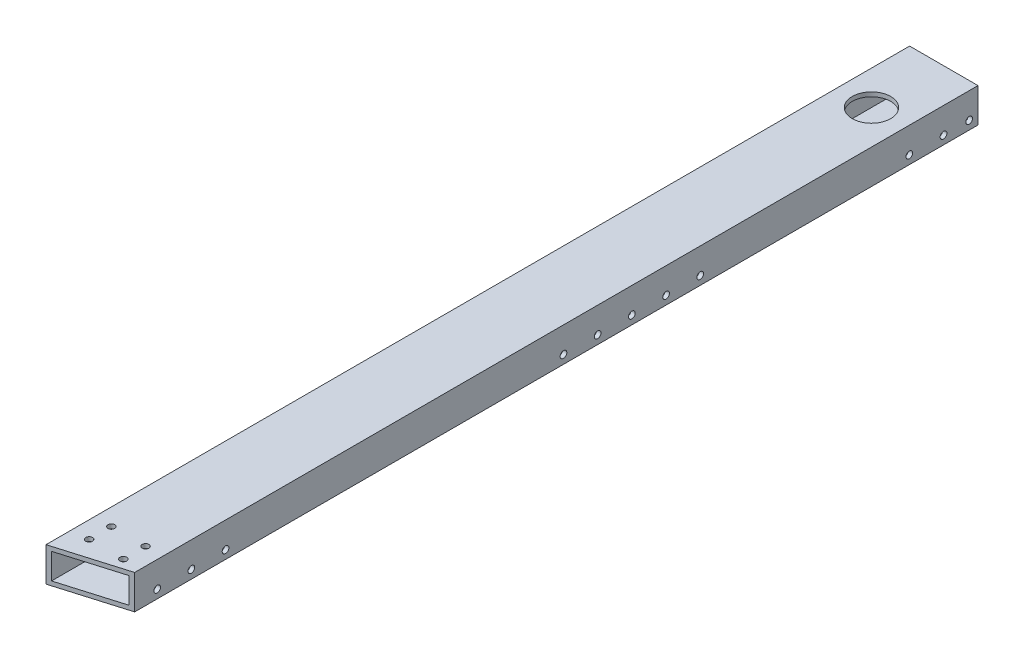
SolidWorks part; units mm, degrees
ref_plane "Front Plane" through (0, 0, 0) normal (0, 0, 1) x (1, 0, 0)
ref_plane "Top Plane" through (0, 0, 0) normal (0, 1, 0) x (1, 0, 0)
ref_plane "Right Plane" through (0, 0, 0) normal (1, 0, 0) x (0, 0, -1)
sketch "Sketch1" plane through (0, 0, 0) normal (0, 0, 1) x (1, 0, 0)
  line L0 (-22.225, 9.525) -> (22.225, 9.525)
  line L2 (-25.4, 12.7) -> (25.4, 12.7)
  line L3 (-25.4, 12.7) -> (-25.4, -12.7)
  line L4 (-25.4, -12.7) -> (25.4, -12.7)
  line L5 (25.4, 12.7) -> (25.4, -12.7)
  line L10 (22.225, 9.525) -> (22.225, -9.525)
  line L11 (-22.225, -9.525) -> (22.225, -9.525)
  line L12 (-22.225, 9.525) -> (-22.225, -9.525)
  point P12 (0, 12.7)
  point P14 (25.4, 0)
  dimension "Wall Thickness" = 3.175
  dimension "Outside Width" = 50.8
  dimension "Outside Height" = 25.4
  dimension "Inside Height" = 19.05
  dimension "Inside Width" = 44.45
sketch "Sketch2" plane through (0, 0, 0) normal (1, 0, 0) x (0, 0, -1)
  line L0 (320.675, 0) -> (-320.675, 0)
  point P4 (0, 0)
  point P7 (-320.675, 0)
  point P10 (320.675, 0)
  dimension "Length" = 641.35
sketch "Sketch3" plane through (0, 0, 0) normal (0, 0, 1) x (1, 0, 0)
  line L21 (25.4, 12.7) -> (-25.4, 12.7)
  line L22 (25.4, -12.7) -> (25.4, 12.7)
  line L23 (-25.4, -12.7) -> (25.4, -12.7)
  line L24 (-25.4, 12.7) -> (-25.4, -12.7)
  line L25 (25.4, 12.7) -> (-25.4, 12.7)
  line L26 (25.4, -12.7) -> (25.4, 12.7)
  line L27 (-25.4, -12.7) -> (25.4, -12.7)
  line L28 (-25.4, 12.7) -> (-25.4, -12.7)
  line L29 (22.225, 9.525) -> (-22.225, 9.525)
  line L30 (22.225, -9.525) -> (22.225, 9.525)
  line L31 (-22.225, -9.525) -> (22.225, -9.525)
  line L32 (-22.225, 9.525) -> (-22.225, -9.525)
  line L33 (22.225, 9.525) -> (-22.225, 9.525)
  line L34 (22.225, -9.525) -> (22.225, 9.525)
  line L35 (-22.225, -9.525) -> (22.225, -9.525)
  line L36 (-22.225, 9.525) -> (-22.225, -9.525)
  dimension "D1" = 0
  dimension "D2" = 0
extrude "Boss-Extrude1" add sketch "Sketch3" along normal up to vertex (320.675 mm away) and the other way up to vertex (320.675 mm away) up to point (0, 0, 320.675) other way up to point (0, 0, -320.675)
sketch "Drawing Reference" plane through (0, 0, 0) normal (1, 0, 0) x (0, 0, -1)
  line L0 (-320.675, 0) -> (320.675, 0) construction
  line L1 (0, -12.7) -> (0, 12.7) construction
  line L2 (-320.675, -12.7) -> (320.675, -12.7) construction
  line L5 (-320.675, 12.7) -> (320.675, 12.7) construction
  point P7 (-284.099, 0)
  point P8 (284.099, 0)
  dimension "D1" = 36.576
sketch "Sketch4" plane through (0, 12.7, 0) normal (0, 1, 0) x (1, 0, 0)
  line L0 (-25.4, -320.675) -> (25.4, -305.6274)
  line L1 (25.4, -320.675) -> (25.4, 320.675) construction
  line L2 (25.4, -320.675) -> (-25.4, -320.675)
  dimension "D1" = 16.5
extrude "Cut-Extrude1" cut sketch "Sketch4" against normal through all and the other way through all flip side to cut
sketch "Sketch8" plane through (0, 12.7, 0) normal (0, 1, 0) x (1, 0, 0)
  line L0 (0, 320.675) -> (0, 266.954) construction
  line L1 (25.4, 320.675) -> (-25.4, 320.675) construction
  circle A0 centre (0, 266.954) radius 14.2875
  dimension "D1" = 53.721
extrude "Cut-Extrude2" cut sketch "Sketch8" against normal through all
sketch "Sketch9" plane through (0, 12.7, 0) normal (0, 1, 0) x (1, 0, 0)
  line L0 (-12.7762, -284.753) -> (12.6238, -284.753) construction
  line L1 (12.6238, -284.753) -> (12.6238, -301.263) construction
  line L2 (12.6238, -301.263) -> (-12.7762, -301.263) construction
  line L3 (-12.7762, -301.263) -> (-12.7762, -284.753) construction
hole_wizard "#10 Clearance Hole1" positions "Sketch10" profile "Sketch11" hole size "#10" standard "ANSI Inch"
sketch "Sketch10" plane through (0, 12.7, 0) normal (0, 1, 0) x (1, 0, 0)
  point P0 (-12.7762, -284.753)
  point P3 (12.6238, -284.753)
  point P6 (12.6238, -301.263)
  point P9 (-12.7762, -301.263)
sketch "Sketch11" plane through (-12.7762, 12.7, 284.753) normal (1, 0, 0) x (0, 0, 1)
  line L0 (0, 0) -> (0, 6.5757)
  line L1 (0, 6.5757) -> (2.4892, 5.08)
  line L2 (2.4892, 5.08) -> (2.4892, 0)
  line L5 (2.4892, 0) -> (0, 0)
  line L10 (0, 6.5757) -> (-2.4892, 5.08) construction
  line L11 (0, -6.35) -> (0, 107.95) construction
  dimension "Hole Dia." = 4.9784
  dimension "Hole Depth" = 5.08
  dimension "Drill Angle" = 118
hole_wizard "#10 Clearance Hole2" positions "Sketch12" profile "Sketch13" hole size "#10" standard "ANSI Inch" end condition through all
sketch "Sketch12" plane through (25.4, 0, 0) normal (1, 0, 0) x (0, 0, -1)
  point P9 (12.827, -6.35)
  point P12 (38.227, -6.35)
  point P15 (63.627, -6.35)
  point P18 (89.027, -6.35)
  point P21 (114.427, -6.35)
  point P24 (-288.925, -6.35)
  point P27 (-263.525, -6.35)
  point P30 (-238.1261, -6.3882)
sketch "Sketch13" plane through (25.4, -6.35, -12.827) normal (0, 1, 0) x (0, 0, -1)
  line L0 (0, 0) -> (0, 50.8)
  line L1 (0, 50.8) -> (2.4892, 50.8)
  line L2 (2.4892, 50.8) -> (2.4892, 0)
  line L5 (2.4892, 0) -> (0, 0)
  line L11 (0, -6.35) -> (0, 107.95) construction
  dimension "Thru Hole Dia." = 4.9784
  dimension "Thru Hole Depth" = 50.8
hole_wizard "#10 Clearance Hole3" positions "Sketch14" profile "Sketch15" hole size "#10" standard "ANSI Inch"
sketch "Sketch14" plane through (25.4, 0, 0) normal (1, 0, 0) x (0, 0, -1)
  point P0 (269.6733, -6.3882)
  point P3 (295.0733, -6.3882)
  point P6 (314.1233, -6.3882)
sketch "Sketch15" plane through (25.4, -6.3882, -269.6733) normal (0, 1, 0) x (0, 0, -1)
  line L0 (0, 0) -> (0, 4.7977)
  line L1 (0, 4.7977) -> (2.4892, 3.302)
  line L2 (2.4892, 3.302) -> (2.4892, 0)
  line L5 (2.4892, 0) -> (0, 0)
  line L10 (0, 4.7977) -> (-2.4892, 3.302) construction
  line L11 (0, -6.35) -> (0, 107.95) construction
  dimension "Hole Dia." = 4.9784
  dimension "Hole Depth" = 3.302
  dimension "Drill Angle" = 118
equation "\"D1@Drawing Reference\"=\"Outside Width@Sketch1\" * 0.72"
